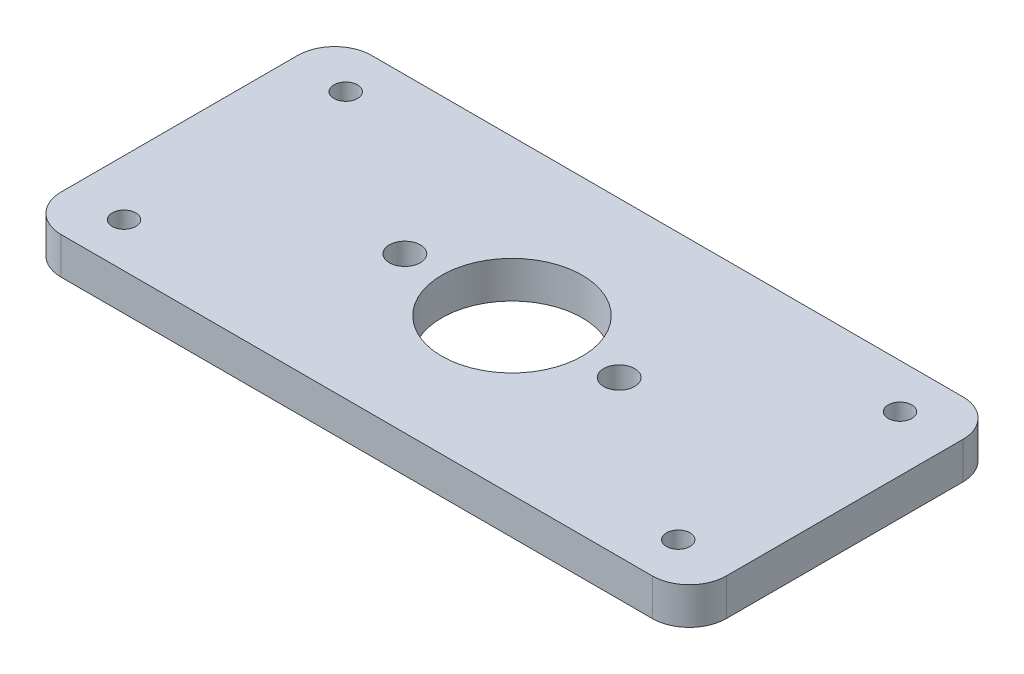
SolidWorks part; units mm, degrees
material "Acrylic (Medium-high impact)"
ref_plane "Front Plane" through (0, 0, 0) normal (0, 0, 1) x (1, 0, 0)
ref_plane "Top Plane" through (0, 0, 0) normal (0, 1, 0) x (1, 0, 0)
ref_plane "Right Plane" through (0, 0, 0) normal (1, 0, 0) x (0, 0, -1)
sketch "Sketch1" plane through (0, 0, 0) normal (0, 1, 0) x (1, 0, 0)
  line L0 (0, 21) -> (90, 21) construction
  line L1 (0, 0) -> (90, 0)
  line L2 (0, 0) -> (0, 42)
  line L3 (0, 42) -> (90, 42)
  line L4 (90, 0) -> (90, 42)
  line L5 (45, 42) -> (45, 0) construction
  line L6 (7.5, 42) -> (7.5, 0) construction
  circle A0 centre (45, 21) radius 9.5
  circle A1 centre (59.5, 21) radius 2.1
  circle A2 centre (30.5, 21) radius 2.1
  circle A3 centre (7.5, 36) radius 1.6
  circle A4 centre (7.5, 6) radius 1.6
  circle A5 centre (82.5, 6) radius 1.6
  circle A6 centre (82.5, 36) radius 1.6
  dimension "D3" = 19
  dimension "D4" = 4.2
  dimension "D5" = 29
  dimension "D6" = 3.2
  dimension "D7" = 30
  dimension "D1" = 90
  dimension "D2" = 42
  dimension "D8" = 7.5
extrude "Boss-Extrude1" add sketch "Sketch1" along normal blind 5
fillet "Fillet1" radius 5 4 edges at (90, 2.5, -42) (90, 2.5, 0) (0, 2.5, 0) (0, 2.5, -42)
